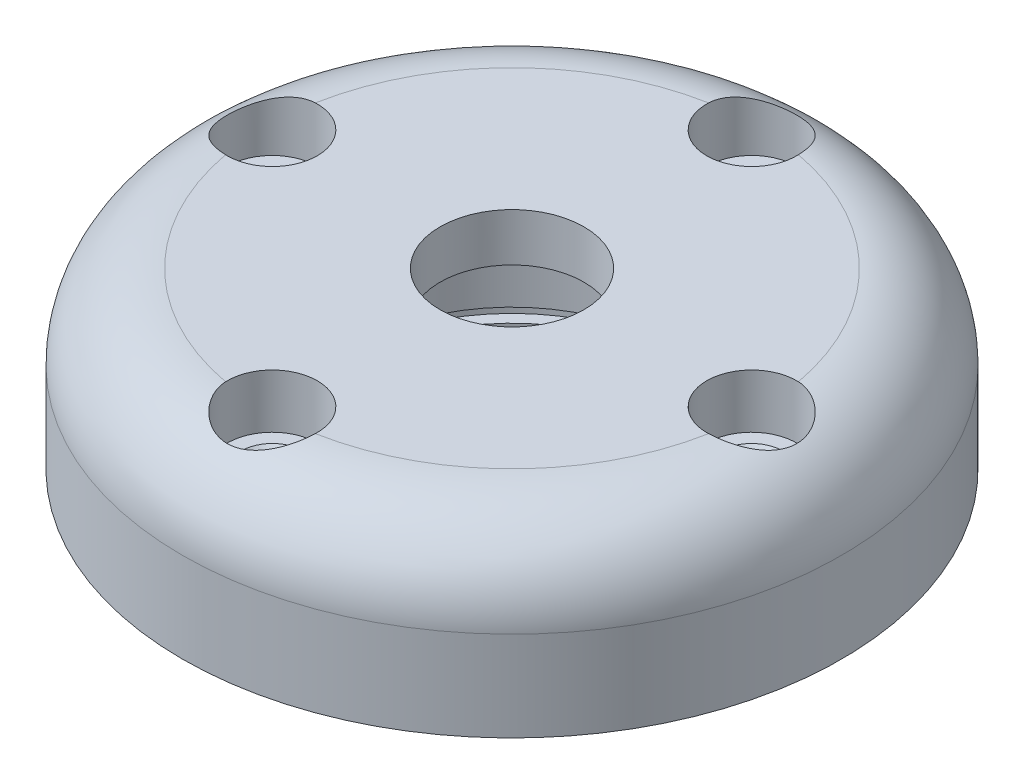
SolidWorks part; units mm, degrees
material "ABS"
ref_plane "Front Plane" through (0, 0, 0) normal (0, 0, 1) x (1, 0, 0)
ref_plane "Top Plane" through (0, 0, 0) normal (0, 1, 0) x (1, 0, 0)
ref_plane "Right Plane" through (0, 0, 0) normal (1, 0, 0) x (0, 0, -1)
sketch "Sketch1" plane through (0, 0, 0) normal (0, 1, 0) x (1, 0, 0)
  circle A0 centre (0, 0) radius 27.5
  circle A2 centre (0, 0) radius 13
  circle A3 centre (0, 0) radius 14
  dimension "D1" = 55
  dimension "D3" = 26
  dimension "D4" = 28
extrude "Boss-Extrude1" add sketch "Sketch1" along normal blind 18 from offset 3 contours A0 region at (-26.7222, 0, 0)
extrude "Boss-Extrude2" add sketch "Sketch1<3>" against normal blind 3 from surface contours A3 starting at face at (0, 21, 14)
sketch "Sketch1<3>" plane through (0, 0, 0) normal (0, 1, 0) x (1, 0, 0) same geometry as "Sketch1"
extrude "Boss-Extrude3" add sketch "Sketch1<4>" along normal up to surface (18 mm away) from offset 9 contours A3 region at (-13.604, 0, 0) up to face at (0, 18, 14)
sketch "Sketch1<4>" plane through (0, 0, 0) normal (0, 1, 0) x (1, 0, 0) same geometry as "Sketch1"
sketch "Sketch2" plane through (0, 21, 0) normal (0, 1, 0) x (1, 0, 0)
  circle A0 centre (0, 0) radius 20 construction
  circle A1 centre (0, -20) radius 3.75
  circle A2 centre (-20, 0) radius 3.75
  circle A3 centre (0, 20) radius 3.75
  circle A4 centre (20, 0) radius 3.75
  circle A5 centre (0, -20) radius 2.1
  circle A6 centre (-20, 0) radius 2.1
  circle A7 centre (0, 20) radius 2.1
  circle A8 centre (20, 0) radius 2.1
  point P13 (0, 0)
  point P21 (0, 0)
  dimension "D1" = 7.5
  dimension "D3" = 40
  dimension "D4" = 4.2
  dimension "D2" = 4
  dimension "D5" = 4
extrude "Cut-Extrude1" cut sketch "Sketch2" against normal up to next contours A5 | A6 | A8 | A7 region at (0, 21, 20)
extrude "Cut-Extrude2" cut sketch "Sketch2<3>" against normal blind 4.5
sketch "Sketch2<3>" plane through (0, 21, 0) normal (0, 1, 0) x (1, 0, 0) same geometry as "Sketch2"
chamfer "Chamfer1" distance 0.5 angle 45 4 edges at (20, 16.5, 2.1) (0, 16.5, 22.1) (-20, 16.5, 2.1) (0, 16.5, -17.9)
extrude "Boss-Extrude4" add sketch "Sketch1<6>" along normal blind 4.84 from offset 3 contours A3 | A2
sketch "Sketch1<6>" plane through (0, 0, 0) normal (0, 1, 0) x (1, 0, 0) same geometry as "Sketch1"
sketch "Sketch3" plane through (0, 18, 0) normal (0, -1, 0) x (1, 0, 0)
  circle A0 centre (0, 0) radius 13
extrude "Boss-Extrude5" add sketch "Sketch3" along normal blind 1
sketch "Sketch4" plane through (0, 3, 0) normal (0, -1, 0) x (1, 0, 0)
  circle A0 centre (0, 0) radius 35
  dimension "D1" = 70
extrude "Cut-Extrude3" cut sketch "Sketch4" against normal blind 3.5
sketch "Sketch5" plane through (0, 17, 0) normal (0, -1, 0) x (1, 0, 0)
  circle A0 centre (0, 0) radius 6
  dimension "D1" = 12
extrude "Cut-Extrude5" cut sketch "Sketch5" against normal up to next
fillet "Fillet1" radius 7 1 edges at (0, 21, 27.5)
sketch "Sketch6" [suppressed] plane through (0, 21, 0) normal (0, 1, 0) x (1, 0, 0)
  line L0 (-10.7102, 17.4797) -> (-5.69, 26.9049)
  line L1 (-14.4957, 14.4957) -> (-8.8937, 8.8937) construction
  line L2 (-17.4797, 10.7102) -> (-26.9049, 5.69)
  arc A1 (-3.7468, 20.1547) -> (-20.1547, 3.7468) centre (0, 0) ccw construction
  circle A2 centre (0, 0) radius 27.5 construction
  arc A3 (-5.69, 26.9049) -> (-26.9049, 5.69) centre (0, 0) ccw
  arc A4 (-17.4797, 10.7102) -> (-10.7102, 17.4797) centre (-14.4957, 14.4957) ccw
